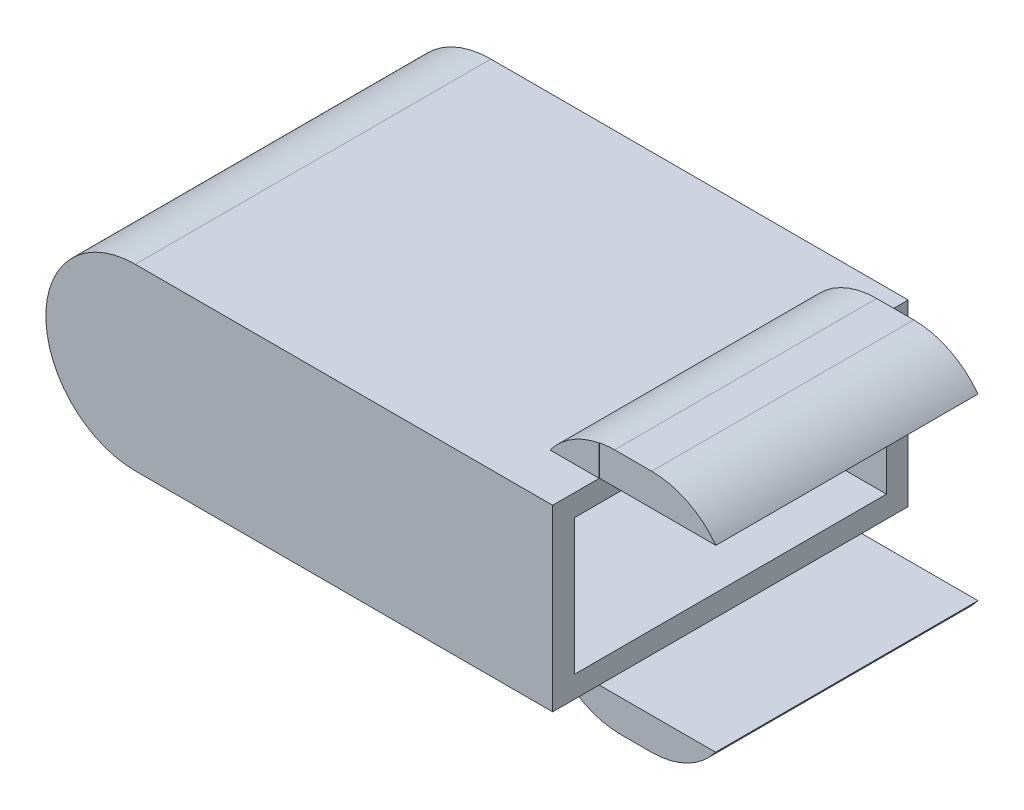
SolidWorks part; units mm, degrees
ref_plane "Plan de face" through (0, 0, 0) normal (0, 0, 1) x (1, 0, 0)
ref_plane "Plan de dessus" through (0, 0, 0) normal (0, 1, 0) x (1, 0, 0)
ref_plane "Plan de droite" through (0, 0, 0) normal (1, 0, 0) x (0, 0, -1)
sketch "Esquisse1" plane through (0, 0, 0) normal (0, 1, 0) x (1, 0, 0)
  line L1 (18.2408, 22.15) -> (-33.7592, 22.15)
  line L2 (18.2408, 22.15) -> (18.2408, -22.15)
  line L3 (18.2408, -22.15) -> (-33.7592, -22.15)
  line L4 (-33.7592, 22.15) -> (-33.7592, -22.15)
  line L5 (18.2408, 22.15) -> (-33.7592, -22.15) construction
  line L6 (18.2408, -22.15) -> (-33.7592, 22.15) construction
  point P0 (-7.7592, 0)
  dimension "D1" = 44.3
  dimension "D2" = 52
extrude "Boss.-Extru.1" add sketch "Esquisse1" along normal blind 22.3
sketch "Esquisse4" plane through (18.2408, 0, 0) normal (1, 0, 0) x (0, 0, -1)
  line L0 (-22.15, 22.3) -> (22.15, 0) construction
  line L1 (22.15, 22.3) -> (22.15, 0) construction
  line L2 (-19.45, 2.7) -> (19.45, 2.7)
  line L3 (-19.45, 2.7) -> (-19.45, 19.6)
  line L4 (-19.45, 19.6) -> (19.45, 19.6)
  line L5 (19.45, 2.7) -> (19.45, 19.6)
  line L6 (-19.45, 2.7) -> (19.45, 19.6) construction
  line L7 (-19.45, 19.6) -> (19.45, 2.7) construction
  line L8 (-22.15, 22.3) -> (22.15, 22.3) construction
  point P4 (0, 11.15)
  point P13 (0, 22.3)
  dimension "D1" = 2.7
  dimension "D2" = 2.7
extrude "Enlèv. mat.-Extru.2" cut sketch "Esquisse4" against normal up to vertex (52 mm away) up to point (-33.7592, 0, -22.15)
sketch "Esquisse5" plane through (0, 0, 22.15) normal (0, 0, 1) x (1, 0, 0)
  line L0 (-33.7592, 22.3) -> (-33.7592, 0) construction
  line L5 (-33.7592, 0) -> (18.2408, 0)
  line L6 (18.2408, 0) -> (18.2408, 22.3)
  line L7 (18.2408, 22.3) -> (-33.7592, 22.3)
  line L8 (-33.7592, 22.3) -> (-33.7592, 0)
  line L12 (-33.7592, 22.3) -> (-33.7592, 0)
  arc A0 (-33.7592, 22.3) -> (-33.7592, 0) centre (-33.7592, 11.15) ccw
  dimension "D1" = 0
extrude "Boss.-Extru.3" add sketch "Esquisse5" against normal up to vertex (44.3 mm away) up to point (-33.7592, 0, -22.15)
sketch "Esquisse9" plane through (0, 0, 0) normal (0, -1, 0) x (1, 0, 0)
  line L0 (18.2408, -16.35) -> (12.9175, -16.35)
  line L1 (18.2408, -16.35) -> (18.2408, 16.35)
  line L2 (12.9175, -16.35) -> (12.9175, 16.35)
  line L3 (18.2408, 16.35) -> (12.9175, 16.35)
  line L4 (18.2408, 22.15) -> (18.2408, -22.15) construction
  line L5 (18.2408, -22.15) -> (-33.7592, -22.15) construction
  line L6 (-33.7592, 22.15) -> (18.2408, 22.15) construction
  dimension "D1" = 5.8
  dimension "D2" = 5.8
extrude "Boss.-Extru.4" add sketch "Esquisse9" along normal blind 4
sketch "Esquisse10" plane through (18.2408, 0, 0) normal (1, 0, 0) x (0, 0, -1)
  line L0 (16.35, 0) -> (16.35, -4)
  line L1 (16.35, 0) -> (-16.35, 0)
  line L2 (16.35, -4) -> (-16.35, -4)
  line L3 (-16.35, 0) -> (-16.35, -4)
  line L4 (-16.35, -4) -> (-16.35, 0) construction
  line L5 (16.35, -4) -> (-16.35, -4) construction
  point P0 (-16.35, -4)
extrude "Boss.-Extru.5" add sketch "Esquisse10" along normal blind 14.5
sketch "Esquisse11" plane through (0, 22.3, 0) normal (0, 1, 0) x (1, 0, 0)
  line L0 (18.2408, 16.35) -> (18.2408, -16.35)
  line L1 (18.2408, 16.35) -> (12.1182, 16.35)
  line L2 (18.2408, -16.35) -> (12.1182, -16.35)
  line L3 (12.1182, 16.35) -> (12.1182, -16.35)
  line L4 (18.2408, -22.15) -> (18.2408, 22.15) construction
  line L5 (18.2408, 22.15) -> (-33.7592, 22.15) construction
  line L6 (-33.7592, -22.15) -> (18.2408, -22.15) construction
  dimension "D1" = 5.8
  dimension "D2" = 5.8
extrude "Boss.-Extru.6" add sketch "Esquisse11" along normal blind 4 contours L3 L2 L0 L1
sketch "Esquisse12" plane through (18.2408, 0, 0) normal (1, 0, 0) x (0, 0, -1)
  line L0 (16.35, 22.3) -> (16.35, 26.3)
  line L1 (16.35, 22.3) -> (-16.3103, 22.3)
  line L2 (16.35, 26.3) -> (-16.3103, 26.3)
  line L3 (-16.3103, 22.3) -> (-16.3103, 26.3)
extrude "Boss.-Extru.7" add sketch "Esquisse12" along normal blind 14.5
fillet "Congé1" radius 10 1 edges at (12.9175, -4, 0)
fillet "Congé2" radius 10 1 edges at (12.1182, 26.3, 0)
fillet "Congé3" radius 10 1 edges at (32.7408, -4, 0)
fillet "Congé4" radius 10 1 edges at (32.7408, 26.3, -0.0199)
